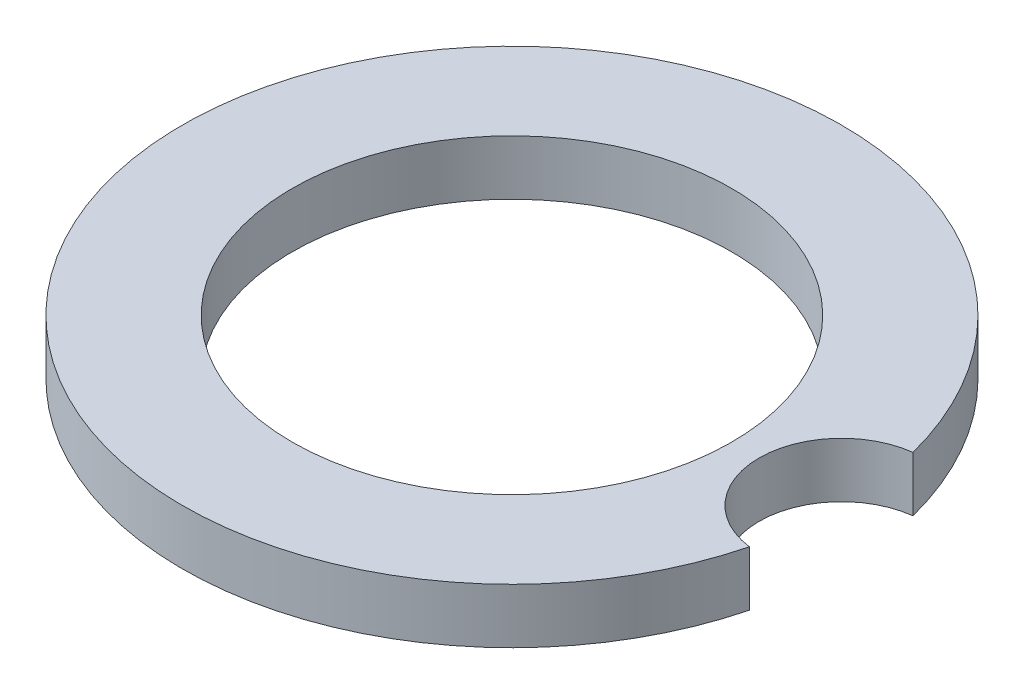
SolidWorks part; units mm, degrees
ref_plane "Front Plane" through (0, 0, 0) normal (0, 0, 1) x (1, 0, 0)
ref_plane "Top Plane" through (0, 0, 0) normal (0, 1, 0) x (1, 0, 0)
ref_plane "Right Plane" through (0, 0, 0) normal (1, 0, 0) x (0, 0, -1)
sketch "Sketch1" plane through (0, 0, 0) normal (0, 1, 0) x (1, 0, 0)
  circle A0 centre (0, 0) radius 50.8
  circle A1 centre (0, 0) radius 76.1746
  dimension "Front_CR_ID" = 101.6
  dimension "Front_CR_OD" = 152.3492
extrude "Boss-Extrude1" add sketch "Sketch1" along normal blind 12.7 contours A1
extrude "Cut-Extrude2" cut sketch "Sketch1<10>" along normal through all contours A0
sketch "Sketch1<10>" plane through (0, 0, 0) normal (0, 1, 0) x (1, 0, 0) same geometry as "Sketch1"
sketch "Sketch2" plane through (0, 12.7, 0) normal (0, 1, 0) x (1, 0, 0)
  line L0 (76.2, 19.05) -> (76.2, -19.05)
  arc A0 (76.2, 19.05) -> (76.2, -19.05) centre (76.1746, 0) ccw
  circle A1 centre (0, 0) radius 76.1746 construction
  dimension "D1" = 38.1
extrude "Cut-Extrude3" cut sketch "Sketch2" against normal through all contours A0 L0
ref_plane "Plane1" through (0, 6.35, 0) normal (0, -1, 0) x (-1, 0, 0)
equation "\"Bodytube_OD\" = 6.17in"
equation "\"Bodytube_ID\" = 5.998in"
equation "\"Motor_OD\" = 4in"
equation "\"Fwd_Tube_Length\" = 40in"
equation "\"Mid_Tube_Length\" = 1in"
equation "\"Aft_Section_Length\"= 39in"
equation "\"Mid_Coupler_Length\"= 13in"
equation "\"Aft_Lower_Length\"= 22in"
equation "\"AB_Coupler_OD_Length\"= 1in"
equation "\"AB_Coupling_Section_Length\"= 0.375in"
equation "\"AB_Coupler_Length\"= \"AB_Coupler_OD_Length\" + \"AB_Coupling_Section_Length\" * 2"
equation "\"Cutout_Angle\" = 80"
equation "\"AB_Paddle_Height\" = 0.375in"
equation "\"AB_Coupler_Num_Screws\"= 6"
equation "\"Num_Cutouts\" = 3"
equation "\"AB_Coupler_OD\"= 6.17in"
equation "\"AB_Coupler_ID\"= 5.75in"
equation "\"AB_Coupler_Surface_Diameter\"= 5.998in"
equation "\"AB_Coupling_Screw_Diameter\"= 0.1065in"
equation "\"AB_Central_Bushing_Length\" = .75in"
equation "\"Lead_Screw_Dist\" = 2.25in"
equation "\"Lead_Screw_Diam\" = (27/64)*1in"
equation "\"Lead_Screw_Length\" = (\"Mid_Coupler_Length\" + 2*0.375in + 2*0.5in)"
equation "\"Paddle_Pin_Offset\" = .25in"
equation "\"Paddle_Pin_Radius\" = 2.25in"
equation "\"Paddle_Gear_OD\" = 3.2in"
equation "\"Fwd_BKHD_From_Top\" = 18in"
equation "\"Front_CR_OD@Sketch1\"=\"Bodytube_ID\""
equation "\"Front_CR_ID@Sketch1\"=\"Motor_OD\""
